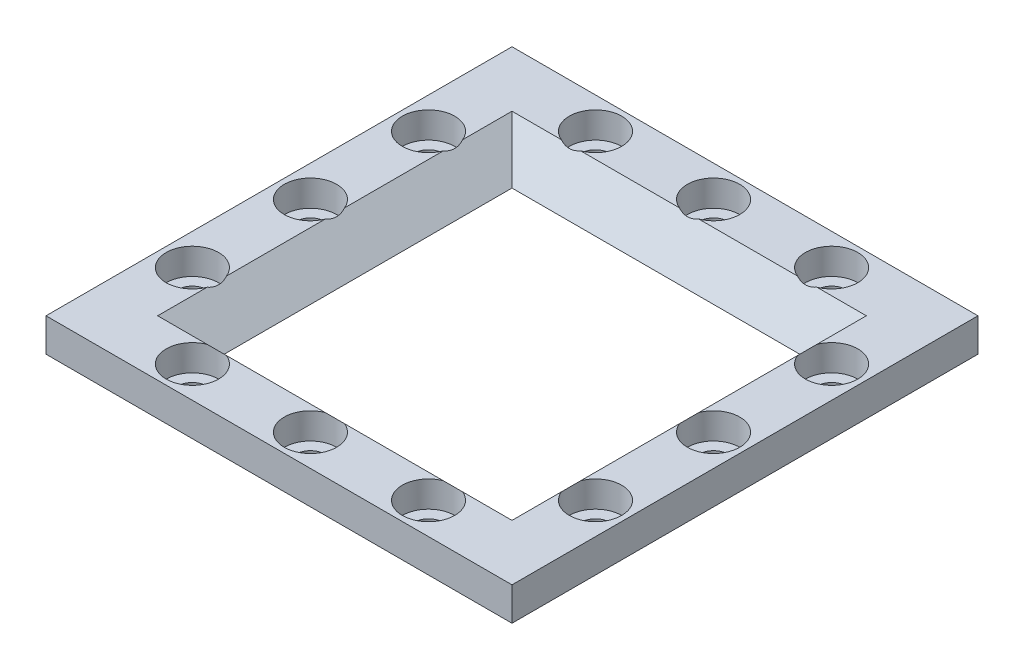
SolidWorks part; units mm, degrees
ref_plane "Front Plane" through (0, 0, 0) normal (0, 0, 1) x (1, 0, 0)
ref_plane "Top Plane" through (0, 0, 0) normal (0, 1, 0) x (1, 0, 0)
ref_plane "Right Plane" through (0, 0, 0) normal (1, 0, 0) x (0, 0, -1)
sketch "Sketch1" plane through (0, 0, 0) normal (0, 1, 0) x (1, 0, 0)
  line L0 (-38.45, 38.45) -> (-22.5235, 38.45) construction
  line L1 (-25, -25) -> (25, -25) construction
  line L2 (-25, -25) -> (-25, 25) construction
  line L3 (-25, 25) -> (25, 25) construction
  line L4 (25, -25) -> (25, 25) construction
  line L5 (-25, -25) -> (25, 25) construction
  line L6 (-25, 25) -> (25, -25) construction
  line L7 (44.45, -44.45) -> (-44.45, -44.45)
  line L8 (44.45, -44.45) -> (44.45, 44.45)
  line L9 (44.45, 44.45) -> (-44.45, 44.45)
  line L10 (-44.45, -44.45) -> (-44.45, 44.45)
  line L11 (44.45, -44.45) -> (-44.45, 44.45) construction
  line L12 (44.45, 44.45) -> (-44.45, -44.45) construction
  line L13 (32.45, -32.45) -> (-32.45, -32.45) construction
  line L14 (32.45, -32.45) -> (32.45, 32.45) construction
  line L15 (32.45, 32.45) -> (-32.45, 32.45) construction
  line L16 (-32.45, -32.45) -> (-32.45, 32.45) construction
  line L17 (32.45, -32.45) -> (-32.45, 32.45) construction
  line L18 (32.45, 32.45) -> (-32.45, -32.45) construction
  line L19 (-22.5235, 38.45) -> (0, 38.45) construction
  line L20 (0, 38.45) -> (22.5235, 38.45) construction
  line L21 (22.5235, 38.45) -> (38.45, 38.45) construction
  line L22 (38.45, 38.45) -> (38.45, 22.5235) construction
  line L23 (38.45, 22.5235) -> (38.45, 0) construction
  line L24 (38.45, 0) -> (38.45, -22.5235) construction
  line L25 (38.45, -22.5235) -> (38.45, -38.45) construction
  line L26 (38.45, -38.45) -> (22.5235, -38.45) construction
  line L27 (22.5235, -38.45) -> (0, -38.45) construction
  line L28 (0, -38.45) -> (-22.5235, -38.45) construction
  line L29 (-22.5235, -38.45) -> (-38.45, -38.45) construction
  line L30 (-38.45, -38.45) -> (-38.45, -22.5235) construction
  line L31 (-38.45, -22.5235) -> (-38.45, 0) construction
  line L32 (-38.45, 0) -> (-38.45, 22.5235) construction
  line L33 (-38.45, 22.5235) -> (-38.45, 38.45) construction
  line L34 (-38.45, 22.5235) -> (-22.5235, 38.45) construction
  line L35 (22.5235, 38.45) -> (38.45, 22.5235) construction
  line L36 (38.45, -22.5235) -> (22.5235, -38.45) construction
  line L37 (-38.45, -22.5235) -> (-22.5235, -38.45) construction
  line L38 (-32.45, 0) -> (-44.45, 0) construction
  line L40 (27.45, -27.45) -> (-27.45, -27.45)
  line L41 (27.45, -27.45) -> (27.45, 27.45)
  line L42 (27.45, 27.45) -> (-27.45, 27.45)
  line L43 (-27.45, -27.45) -> (-27.45, 27.45)
  line L44 (27.45, -27.45) -> (-27.45, 27.45) construction
  line L45 (27.45, 27.45) -> (-27.45, -27.45) construction
  circle A0 centre (-25, 25) radius 5 construction
  circle A1 centre (25, 25) radius 5 construction
  circle A2 centre (25, -25) radius 5 construction
  circle A3 centre (-25, -25) radius 5 construction
  circle A4 centre (-22.5235, 38.45) radius 4.25 construction
  circle A5 centre (0, 38.45) radius 4.25 construction
  circle A6 centre (22.5235, 38.45) radius 4.25 construction
  circle A7 centre (38.45, 22.5235) radius 4.25 construction
  circle A8 centre (38.45, 0) radius 4.25 construction
  circle A9 centre (38.45, -22.5235) radius 4.25 construction
  circle A10 centre (22.5235, -38.45) radius 4.25 construction
  circle A11 centre (0, -38.45) radius 4.25 construction
  circle A12 centre (-22.5235, -38.45) radius 4.25 construction
  circle A13 centre (-38.45, -22.5235) radius 4.25 construction
  circle A14 centre (-38.45, 0) radius 4.25 construction
  circle A15 centre (-38.45, 22.5235) radius 4.25 construction
  point P0 (0, 0)
  point P6 (0, 0)
  point P11 (0, 0)
  point P51 (0, 0)
  dimension "D4" = 10
  dimension "D5" = 8.5
  dimension "D1" = 50
  dimension "D2" = 64.9
  dimension "D3" = 12
  dimension "D6" = 5
  dimension "D7" = 88.9
extrude "Boss-Extrude1" add sketch "Sketch1" along normal blind 6.35
chamfer "Chamfer1" distance 6.35 angle 45 4 edges at (0, 6.35, 27.45) (27.45, 6.35, 0) (-27.45, 6.35, 0) (0, 6.35, -27.45)
hole_wizard "CBORE for M5 SHCS3" positions "Sketch2" profile "Sketch4" counterbore size "M5" standard "ANSI Metric" end condition through all
sketch "Sketch2" plane through (0, 6.35, 0) normal (0, 1, 0) x (1, 0, 0)
  line L0 (-32.45, 0) -> (-44.45, 0) construction
  point P0 (-22.5235, 38.45)
  point P3 (0, 38.45)
  point P6 (22.5235, 38.45)
  point P9 (38.45, 22.5235)
  point P12 (38.45, 0)
  point P15 (38.45, -22.5235)
  point P18 (22.5235, -38.45)
  point P21 (0, -38.45)
  point P24 (-22.5235, -38.45)
  point P27 (-38.45, -22.5235)
  point P30 (-38.45, 0)
  point P34 (-38.45, 22.5235)
  point P41 (0, 0)
sketch "Sketch4" plane through (-22.5235, 6.35, -38.45) normal (1, 0, 0) x (0, 0, 1)
  line L0 (0, 0) -> (0, 6.35)
  line L1 (0, 6.35) -> (2.75, 6.35)
  line L3 (2.75, 6.35) -> (2.75, 5)
  line L4 (2.75, 5) -> (5, 5)
  line L5 (5, 5) -> (5, 0)
  line L7 (5, 0) -> (0, 0)
  line L11 (0, -6.35) -> (0, 107.95) construction
  dimension "Thru Hole Dia." = 5.5
  dimension "Thru Hole Depth" = 6.35
  dimension "C'Bore Dia." = 10
  dimension "C'Bore Depth" = 5
